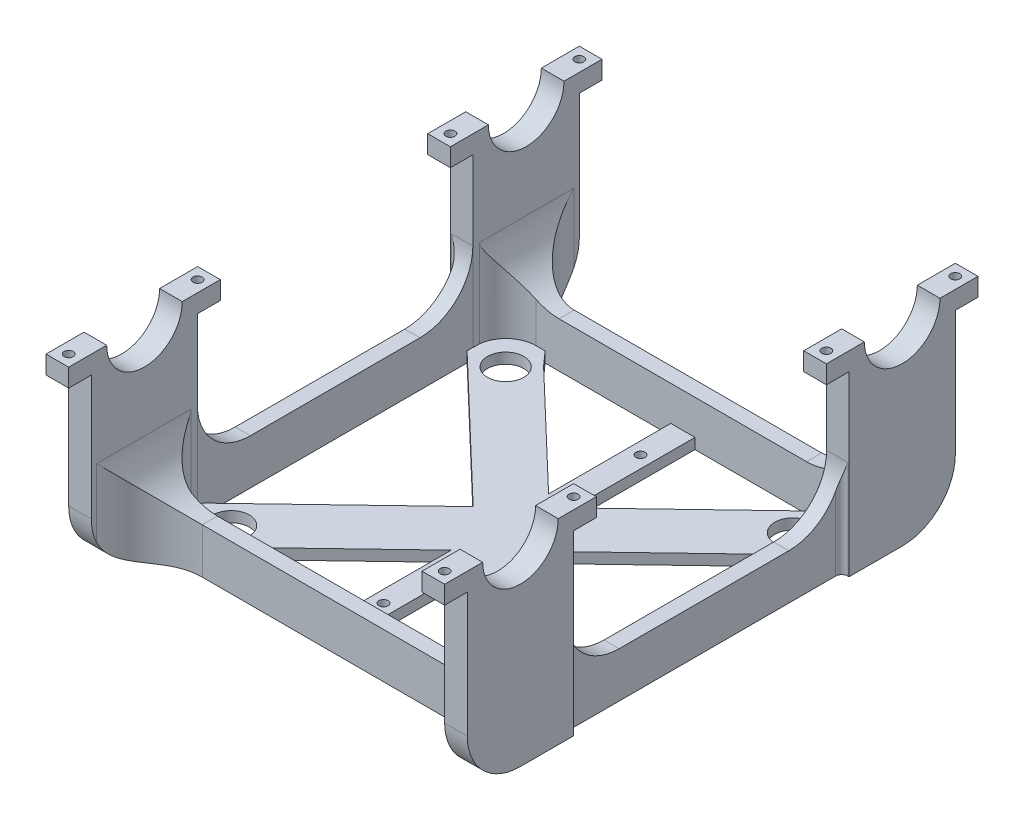
SolidWorks part; units mm, degrees
material "ABS"
ref_plane "Front Plane" through (0, 0, 0) normal (0, 0, 1) x (1, 0, 0)
ref_plane "Top Plane" through (0, 0, 0) normal (0, 1, 0) x (1, 0, 0)
ref_plane "Right Plane" through (0, 0, 0) normal (1, 0, 0) x (0, 0, -1)
sketch "Sketch1" plane through (0, 0, 0) normal (0, 1, 0) x (1, 0, 0)
  line L0 (-58.5, -56.5) -> (58.5, -56.5)
  line L1 (-58.5, -56.5) -> (-58.5, 56.5)
  line L2 (58.5, -56.5) -> (58.5, 56.5)
  line L3 (-58.5, 56.5) -> (58.5, 56.5)
  line L4 (-58.5, -56.5) -> (58.5, 56.5) construction
  line L5 (58.5, -56.5) -> (-58.5, 56.5) construction
  line L6 (-63.5, -61.5) -> (-63.5, 61.5)
  line L7 (-63.5, 61.5) -> (63.5, 61.5)
  line L8 (63.5, -61.5) -> (63.5, 61.5)
  line L9 (-63.5, -61.5) -> (63.5, -61.5)
  point P1 (0, 0)
  dimension "D1" = 117
  dimension "D2" = 113
  dimension "D3" = 5
extrude "Boss-Extrude1" add sketch "Sketch1" along normal blind 15
fillet "Fillet1" radius 10 1 edges at (58.5, 7.5, -56.5)
fillet "Fillet2" radius 10 1 edges at (-58.5, 7.5, -56.5)
fillet "Fillet3" radius 10 1 edges at (-58.5, 7.5, 56.5)
fillet "Fillet4" radius 10 1 edges at (58.5, 7.5, 56.5)
sketch "Sketch4" plane through (0, 15, 0) normal (0, 1, 0) x (1, 0, 0)
  line L0 (-63.5, 61.5) -> (-63.5, 63.125)
  line L1 (-63.5, 63.125) -> (-62.175, 63.125)
  line L2 (-62.175, 63.125) -> (-62.175, 80.6975)
  line L3 (-62.175, 80.6975) -> (-58.425, 80.6975)
  line L4 (-65.925, 45.5525) -> (-65.925, 80.6975)
  line L5 (-65.925, 45.5525) -> (-58.425, 45.5525)
  line L6 (-65.925, 80.6975) -> (-58.425, 80.6975)
  line L7 (-58.425, 45.5525) -> (-58.425, 80.6975)
  line L8 (-65.925, 45.5525) -> (-58.425, 80.6975) construction
  line L9 (-65.925, 80.6975) -> (-58.425, 45.5525) construction
  dimension "D1" = 1.625
  dimension "D2" = 1.325
  dimension "D3" = 3.75
extrude "Boss-Extrude3" add sketch "Sketch4" along normal blind 49.75 and the other way up to surface contours L6 L4 L5 L7
sketch "Sketch5" plane through (-58.425, 0, 0) normal (1, 0, 0) x (0, 0, -1)
  line L0 (45.5525, 64.75) -> (80.6975, 64.75) construction
  circle A0 centre (63.125, 64.75) radius 12.5
  dimension "D1" = 25
extrude "Cut-Extrude1" cut sketch "Sketch5" against normal through all
ref_plane "Plane1" through (-62.175, 0, 0) normal (1, 0, 0) x (0, 0, -1)
sketch "Sketch6" plane through (-58.425, 0, 0) normal (1, 0, 0) x (0, 0, -1)
  line L0 (45.5525, 64.75) -> (50.625, 64.75)
  line L1 (45.5525, 64.75) -> (45.5525, 57.25)
  line L2 (45.5525, 0) -> (45.5525, 64.75) construction
  line L3 (45.5525, 57.25) -> (53.125, 57.25)
  arc A0 (50.625, 64.75) -> (75.625, 64.75) centre (63.125, 64.75) ccw construction
  arc A1 (53.125, 57.25) -> (50.625, 64.75) centre (63.125, 64.75) cw
  dimension "D1" = 7.5
extrude "Boss-Extrude4" add sketch "Sketch6" along normal blind 5
sketch "Sketch9" plane through (0, 64.75, 0) normal (0, 1, 0) x (1, 0, 0)
  line L0 (-53.425, 48.0887) -> (-55.925, 48.0887)
  line L1 (-53.425, 50.625) -> (-53.425, 45.5525) construction
  circle A0 centre (-55.925, 48.0887) radius 1.25
  dimension "D2" = 2.5
  dimension "D1" = 2.5
extrude "Cut-Extrude3" cut sketch "Sketch9" against normal through all
mirror "Mirror1" about plane through (-62.175, 0, 0) normal (1, 0, 0) of "Cut-Extrude3", "Boss-Extrude4"
ref_plane "Plane2" through (0, 0, -63.125) normal (0, 0, -1) x (-1, 0, 0)
mirror "Mirror2" about plane through (0, 0, -63.125) normal (0, 0, -1) of "Mirror1", "Boss-Extrude4", "Cut-Extrude3"
fillet "Fillet6" radius 17.5 1 edges at (-58.425, 7.5, -61.5)
fillet "Fillet7" radius 17.5 3 edges at (-53.2994, 15, -66.6256) (-55.1248, 15, -53.9908) (-58.425, 15, -63.3612)
fillet "Fillet8" radius 2 1 edges at (-63.5, 7.5, -45.5525)
fillet "Fillet9" radius 17.5 2 edges at (-64.0858, 15, -44.9667) (-62, 15, -45.5525)
fillet "Fillet10" radius 17.5 2 edges at (-58.425, 0, -79.8488) (-62.175, 0, -80.6975)
mirror "Mirror4" about plane through (0, 0, 0) normal (0, 0, 1) of "Mirror2", "Mirror1", "Cut-Extrude3", "Boss-Extrude4", "Cut-Extrude1", "Boss-Extrude3"
fillet "Fillet11" radius 2 1 edges at (-63.5, 7.5, 45.5525)
fillet "Fillet12" radius 17.5 2 edges at (-62, 15, 45.5525) (-64.0858, 15, 44.9667)
fillet "Fillet13" radius 17.5 1 edges at (-58.425, 7.5, 61.5)
fillet "Fillet14" radius 17.5 3 edges at (-55.1248, 15, 53.9908) (-58.425, 15, 63.3612) (-53.2994, 15, 66.6256)
fillet "Fillet15" radius 17.5 2 edges at (-58.425, 0, 79.8488) (-62.175, 0, 80.6975)
mirror "Mirror6" about plane through (0, 0, 0) normal (1, 0, 0) of "Mirror4", "Boss-Extrude3", "Cut-Extrude1", "Boss-Extrude4", "Cut-Extrude3", "Mirror1", "Mirror2"
fillet "Fillet16" radius 2 1 edges at (63.5, 7.5, 45.5525)
fillet "Fillet17" radius 17.5 2 edges at (62, 15, 45.5525) (64.0858, 15, 44.9667)
fillet "Fillet18" radius 2 1 edges at (63.5, 7.5, -45.5525)
fillet "Fillet19" radius 17.5 2 edges at (62, 15, -45.5525) (64.0858, 15, -44.9667)
fillet "Fillet20" radius 17.5 1 edges at (58.425, 7.5, -61.5)
fillet "Fillet21" radius 17.5 3 edges at (55.1248, 15, -53.9908) (58.425, 15, -63.3612) (53.2994, 15, -66.6256)
fillet "Fillet22" radius 17.5 1 edges at (58.425, 7.5, 61.5)
fillet "Fillet23" radius 17.5 3 edges at (58.425, 15, 63.3612) (55.1248, 15, 53.9908) (53.2994, 15, 66.6256)
fillet "Fillet24" radius 17.5 2 edges at (58.425, 0, 79.8488) (62.175, 0, 80.6975)
fillet "Fillet25" radius 17.5 2 edges at (58.425, 0, -79.8488) (62.175, 0, -80.6975)
sketch "Sketch11" plane through (0, 0, 0) normal (0, -1, 0) x (-1, 0, 0)
  line L0 (0, 0) -> (0, 45.4)
  line L1 (0, 45.4) -> (-47.5, 45.4)
  line L3 (-35.6125, 0) -> (35.6125, 0) construction
  line L4 (0, 35.6125) -> (0, -35.6125) construction
  line L5 (-47.5, 45.4) -> (47.5, -45.4)
  line L6 (47.5, -45.4) -> (41.3679, -51.8158)
  line L7 (41.3679, -51.8158) -> (-58.5, 43.6368)
  line L8 (-58.5, -45.5525) -> (-58.5, 45.5525) construction
  line L9 (41.3679, -51.8158) -> (45.5521, -56.5)
  line L10 (48.5, -56.5) -> (-48.5, -56.5) construction
  line L11 (47.5, -45.4) -> (53.7617, -39.1106)
  line L12 (-47.5, 45.4) -> (-41.2244, 51.6756)
  line L13 (-41.2244, 51.6756) -> (53.7617, -39.1106)
  line L14 (53.7617, -39.1106) -> (58.5, -43.6395)
  line L15 (58.5, 45.5525) -> (58.5, -45.5525) construction
  line L16 (-41.2244, 51.6756) -> (-46.272, 56.5)
  line L17 (-48.5, 56.5) -> (48.5, 56.5) construction
  circle A0 centre (-47.5, 45.4) radius 6
  circle A1 centre (-47.5, 45.4) radius 8.875
  circle A4 centre (-47.5, -45.4) radius 8.875
  circle A5 centre (-47.5, -45.4) radius 6
  circle A6 centre (47.5, 45.4) radius 8.875
  circle A7 centre (47.5, 45.4) radius 6
  circle A8 centre (47.5, -45.4) radius 8.875
  circle A9 centre (47.5, -45.4) radius 6
  arc A10 (-58.5, 43.6368) -> (-46.272, 56.5) centre (-48.0688, 45.9644) cw
  arc A11 (45.5521, -56.5) -> (58.5, -43.6395) centre (49.0059, -47.0291) ccw
  line M27 (-58.5, -45.5525) -> (-58.5, 45.5525)
  line M28 (-58.5, 45.5525) -> (-58.425, 45.5525)
  line M29 (-58.425, 45.5525) -> (-58.425, 47.7224)
  arc M30 (-58.425, 47.7224) -> (-48.5, 56.5) centre (-48.5, 46.5) cw
  line M31 (-48.5, 56.5) -> (48.5, 56.5)
  line M35 (58.5, 45.5525) -> (58.5, -45.5525)
  line M36 (58.5, -45.5525) -> (58.425, -45.5525)
  line M37 (58.425, -45.5525) -> (58.425, -47.7224)
  arc M38 (58.425, -47.7224) -> (48.5, -56.5) centre (48.5, -46.5) cw
  line M39 (48.5, -56.5) -> (-48.5, -56.5)
  dimension "D3" = 12
  dimension "D4" = 17.75
  dimension "D1" = 45.4
  dimension "D2" = 47.5
extrude "Boss-Extrude5" add sketch "Sketch11" against normal blind 3.5 contours A8 L9 L14 M39 M38 M37 M36 M35 | A9 L6 A8 L11 | A9 L5 A8 L6 | A9 L11 L13 A8 L5 | A8 L5 A1 L7 | A8 L13 L0 L5 | A1 L5 L0 L13 L1 | A1 L1 L13 | L5 A1 L1 A0 | L1 A1 L12 A0 | A1 L5 A0 L12 L16 | A1 L16 L7 M31 M30 M29 M28 M27
mirror "Mirror7" about plane through (0, 0, 0) normal (0, 0, 1) of "Boss-Extrude5"
sketch "Sketch12" plane through (0, 0, 0) normal (0, -1, 0) x (-1, 0, 0)
  line L0 (0, 0) -> (-4, 0)
  line L1 (0, 0) -> (-0.36, 56.5)
  line L2 (-46.272, 56.5) -> (45.5521, 56.5) construction
  line L3 (4, -56.5079) -> (-4, -56.5079)
  line L4 (4, -56.5079) -> (4, 56.5079)
  line L5 (-4, -56.5079) -> (-4, 56.5079)
  line L6 (4, 56.5079) -> (-4, 56.5079)
  line L7 (4, -56.5079) -> (-4, 56.5079) construction
  line L8 (-4, -56.5079) -> (4, 56.5079) construction
  line M6 (-46.272, -56.5) -> (-0.0015, -12.2754)
  line M7 (-0.0015, -12.2754) -> (41.3679, -51.8158)
  line M9 (45.5521, -56.5) -> (-46.272, -56.5)
  line M13 (41.3679, 51.8158) -> (-0.0015, 12.2754)
  line M14 (-0.0015, 12.2754) -> (-46.272, 56.5)
  line M15 (-46.272, 56.5) -> (45.5521, 56.5)
  dimension "D1" = 4
extrude "Boss-Extrude6" add sketch "Sketch12" against normal up to surface (3.5 mm away) contours L4 L1 M13 M15 M14 | L5 L1 M14 M15 | L5 L4 M9 M7 M6 up to face at (47.5, 3.5, -51.4)
sketch "Sketch13" plane through (0, 0, 0) normal (0, -1, 0) x (-1, 0, 0)
  line L0 (0, 0) -> (0, 42.5)
  circle A0 centre (0, 42.5) radius 1.5
  dimension "D2" = 3
  dimension "D1" = 42.5
extrude "Cut-Extrude4" cut sketch "Sketch13" against normal through all
mirror "Mirror8" about plane through (0, 0, 0) normal (0, 0, 1) of "Cut-Extrude4"
sketch "Sketch14" plane through (0, 57.25, 0) normal (0, -1, 0) x (-1, 0, 0)
  line L1 (65.925, -73.125) -> (70.925, -73.125)
  line L2 (65.925, -73.125) -> (65.925, -80.6975)
  line L3 (65.925, -80.6975) -> (70.925, -80.6975)
  line L4 (70.925, -73.125) -> (70.925, -80.6975)
  line L5 (53.425, -73.125) -> (58.425, -73.125)
  line L6 (53.425, -73.125) -> (53.425, -80.6975)
  line L7 (53.425, -80.6975) -> (58.425, -80.6975)
  line L8 (58.425, -73.125) -> (58.425, -80.6975)
  line L9 (65.925, -53.125) -> (70.925, -53.125)
  line L10 (65.925, -53.125) -> (65.925, -45.5525)
  line L11 (65.925, -45.5525) -> (70.925, -45.5525)
  line L12 (70.925, -53.125) -> (70.925, -45.5525)
  line L13 (58.425, -53.125) -> (53.425, -53.125)
  line L14 (58.425, -53.125) -> (58.425, -45.5525)
  line L15 (58.425, -45.5525) -> (53.425, -45.5525)
  line L16 (53.425, -53.125) -> (53.425, -45.5525)
extrude "Cut-Extrude5" cut sketch "Sketch14" against normal through all
mirror "Mirror9" about plane through (0, 0, 0) normal (0, 0, 1) of "Cut-Extrude5"
mirror "Mirror10" about plane through (0, 0, 0) normal (1, 0, 0) of "Mirror9", "Cut-Extrude5"
sketch "Sketch15" plane through (0, 64.75, 0) normal (0, 1, 0) x (1, 0, 0)
  line L0 (-65.925, -80.6975) -> (-65.925, -88.1975)
  line L2 (-65.925, -88.1975) -> (-58.425, -88.1975)
  line L3 (-65.925, -88.1975) -> (-65.925, -80.6975)
  line L4 (-65.925, -80.6975) -> (-58.425, -80.6975)
  line L5 (-58.425, -88.1975) -> (-58.425, -80.6975)
  line M2 (-65.925, -80.6975) -> (-58.425, -80.6975)
  dimension "D1" = 7.5
extrude "Boss-Extrude7" add sketch "Sketch15" against normal blind 6 contours L2 L5 L0 M2
sketch "Sketch16" plane through (0, 58.75, 0) normal (0, -1, 0) x (-1, 0, 0)
  line L0 (58.425, -84.4475) -> (65.925, -84.4475)
  line L1 (58.425, -88.1975) -> (58.425, -80.6975) construction
  line L2 (65.925, -80.6975) -> (65.925, -88.1975) construction
  circle A0 centre (62.175, -84.4475) radius 1.5
  dimension "D1" = 3
extrude "Cut-Extrude6" cut sketch "Sketch16" against normal through all contours A0
ref_plane "Plane3" through (0, 0, 63.125) normal (0, 0, 1) x (1, 0, 0)
mirror "Mirror11" about plane through (0, 0, 63.125) normal (0, 0, 1) of "Cut-Extrude6", "Boss-Extrude7"
mirror "Mirror12" about plane through (0, 0, 0) normal (0, 0, 1) of "Mirror11", "Cut-Extrude6", "Boss-Extrude7"
mirror "Mirror13" about plane through (0, 0, 0) normal (1, 0, 0) of "Mirror12", "Mirror11", "Cut-Extrude6", "Boss-Extrude7"
ref_plane "Plane4" through (0, 42.25, 0) normal (0, 1, 0) x (1, 0, 0)
